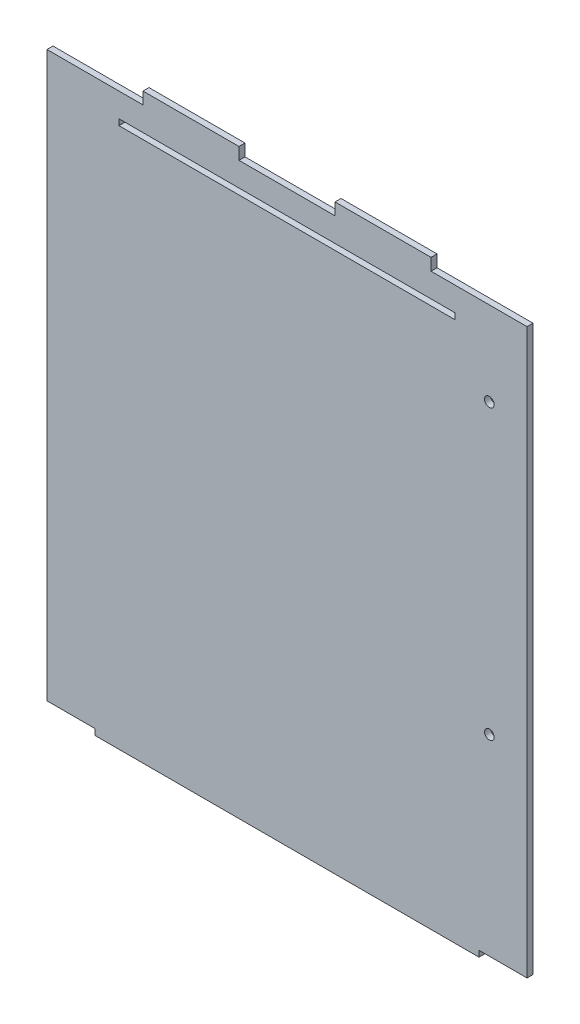
SolidWorks part; units mm, degrees
ref_plane "Front Plane" through (0, 0, 0) normal (0, 0, 1) x (1, 0, 0)
ref_plane "Top Plane" through (0, 0, 0) normal (0, 1, 0) x (1, 0, 0)
ref_plane "Right Plane" through (0, 0, 0) normal (1, 0, 0) x (0, 0, -1)
sketch "Sketch1" plane through (0, 0, 0) normal (0, 0, 1) x (1, 0, 0)
  line L0 (0, 3.175) -> (25.4, 3.175)
  line L1 (25.4, 0) -> (228.6, 0)
  line L2 (0, 3.175) -> (0, 301.625)
  line L3 (50.8, 307.975) -> (101.6, 307.975)
  line L4 (254, 3.175) -> (254, 301.625)
  line L5 (25.4, 3.175) -> (25.4, 0)
  line L6 (25.4, 0) -> (228.6, 0)
  line L7 (0, 301.625) -> (50.8, 301.625)
  line L8 (50.8, 301.625) -> (50.8, 307.975)
  line L9 (50.8, 307.975) -> (101.6, 307.975)
  line L10 (101.6, 307.975) -> (101.6, 301.625)
  line L11 (101.6, 301.625) -> (152.4, 301.625)
  line L12 (152.4, 301.625) -> (152.4, 307.975)
  line L13 (152.4, 307.975) -> (203.2, 307.975)
  line L14 (203.2, 307.975) -> (203.2, 301.625)
  line L15 (203.2, 301.625) -> (254, 301.625)
  line L16 (152.4, 307.975) -> (203.2, 307.975)
  line L17 (228.6, 0) -> (228.6, 3.175)
  line L18 (228.6, 3.175) -> (254, 3.175)
  line L20 (38.1, 288.925) -> (215.9, 288.925)
  line L21 (38.1, 288.925) -> (38.1, 285.75)
  line L22 (38.1, 285.75) -> (215.9, 285.75)
  line L23 (215.9, 288.925) -> (215.9, 285.75)
  dimension "D1" = 307.975
  dimension "D2" = 3.175
  dimension "D3" = 6.35
  dimension "D4" = 50.8
  dimension "D5" = 50.8
  dimension "D6" = 50.8
  dimension "D7" = 50.8
  dimension "D8" = 50.8
  dimension "D9" = 3.175
  dimension "D10" = 25.4
  dimension "D11" = 25.4
  dimension "D12" = 3.175
  dimension "D13" = 177.8
  dimension "D14" = 38.1
  dimension "D15" = 12.7
extrude "Boss-Extrude1" add sketch "Sketch1" along normal blind 3.175 contours L17 L18 L4 L15 L14 L13 L12 L11 L10 L3 L8 L7 L2 L0 L5 L1 L20 L23 L22 L21 region at (127, 151.4181, 0)
sketch "Sketch2" plane through (0, 0, 0) normal (0, 0, -1) x (-1, 0, 0)
  line L0 (-228.6, 3.175) -> (-254, 3.175) construction
  circle A0 centre (-234.0633, 257.175) radius 2.54
  circle A1 centre (-234.0633, 104.775) radius 2.54
  dimension "D1" = 5.08
  dimension "D2" = 101.6
  dimension "D3" = 152.4
extrude "Cut-Extrude1" cut sketch "Sketch2" against normal through all
